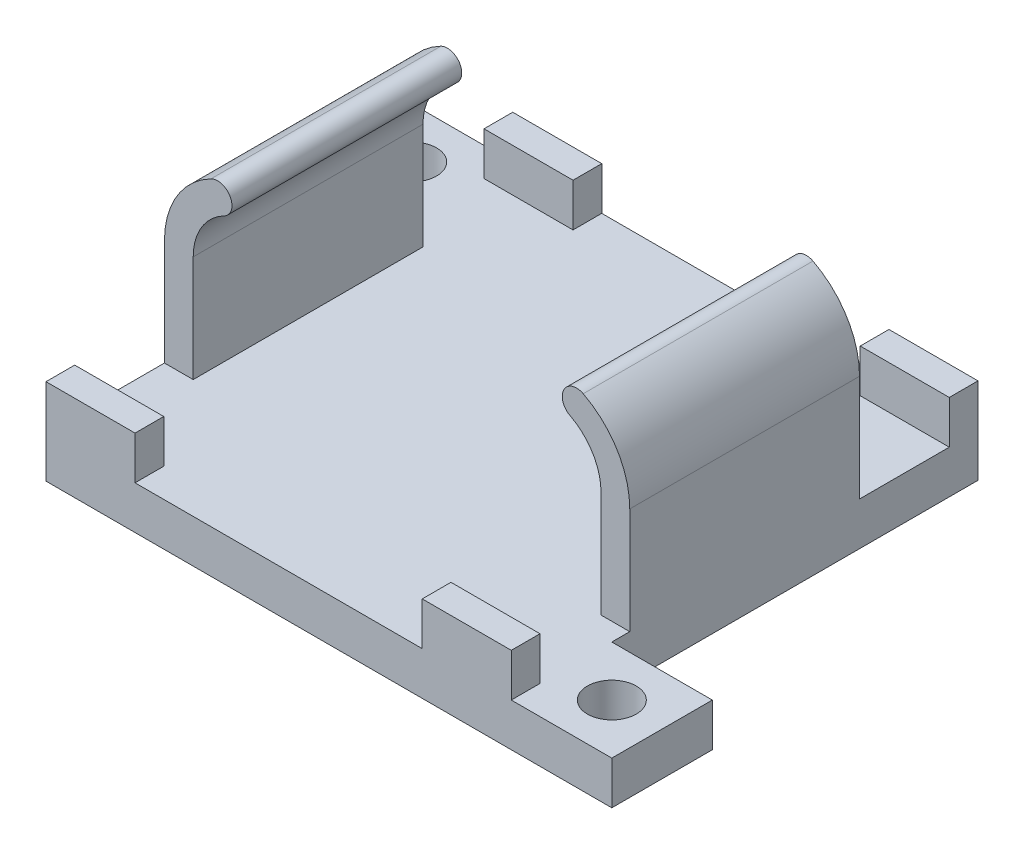
SolidWorks part; units mm, degrees
ref_plane "Front Plane" through (0, 0, 0) normal (0, 0, 1) x (1, 0, 0)
ref_plane "Top Plane" through (0, 0, 0) normal (0, 1, 0) x (1, 0, 0)
ref_plane "Right Plane" through (0, 0, 0) normal (1, 0, 0) x (0, 0, -1)
sketch "Sketch1" plane through (0, 0, 0) normal (0, 0, 1) x (1, 0, 0)
  line L0 (-16.2, -2.2) -> (16.2, -2.2)
  line L1 (-10.2, 8.2) -> (10.2, 8.2)
  line L2 (-16.2, 2.2) -> (-16.2, -8.2)
  line L3 (-16.2, -8.2) -> (16.2, -8.2)
  line L4 (16.2, 2.2) -> (16.2, -8.2)
  line L5 (-16.2, 8.2) -> (16.2, -8.2) construction
  line L6 (-16.2, -8.2) -> (16.2, 8.2) construction
  line L7 (-10.2, 6.2) -> (10.2, 6.2)
  line L8 (-14.2, 2.2) -> (-14.2, -5.2)
  line L9 (-14.2, -5.2) -> (14.2, -5.2)
  line L10 (14.2, 2.2) -> (14.2, -5.2)
  line L11 (-16.2, -5.2) -> (16.2, -5.2)
  line L17 (-10, 4) -> (10, 4)
  line L18 (-10, 4) -> (-10, -5.2)
  line L19 (-10, -5.2) -> (10, -5.2)
  line L20 (10, 4) -> (10, -5.2)
  arc A0 (14.2, 2.2) -> (10.2, 6.2) centre (10.2, 2.2) ccw
  arc A1 (-14.2, 2.2) -> (-10.2, 6.2) centre (-10.2, 2.2) cw
  arc A2 (16.2, 2.2) -> (10.2, 8.2) centre (10.2, 2.2) ccw
  arc A3 (-16.2, 2.2) -> (-10.2, 8.2) centre (-10.2, 2.2) cw
  circle A4 centre (-12.5, 6.6396) radius 1
  circle A5 centre (12.5, 6.6396) radius 1
  point P0 (0, 0)
  point P10 (0, -5.2)
  point P15 (-14.2, 6.2)
  point P30 (0, 0)
  point P35 (0, 4)
  dimension "D5" = 4
  dimension "D6" = 6
  dimension "D9" = 12.5
  dimension "D1" = 11.4
  dimension "D2" = 3
  dimension "D3" = 2
  dimension "D4" = 28.4
  dimension "D7" = 2
  dimension "D8" = 12.5
  dimension "D10" = 4
  dimension "D11" = 20
  dimension "D12" = 3
extrude "Boss-Extrude1" add sketch "Sketch1" along normal blind 14.25 and the other way blind 14.25 contours L11 L2 L3 L4 L9 region at (0, -6.7, 0)
extrude "Boss-Extrude2" add sketch "Sketch1<3>" along normal blind 2 from surface contours L11 L2 L3 L4 L9 | L2 L11 L8 L0 | L18 L0 L8 L9 | L0 L20 L9 L10 | L10 L11 L4 L0 region at (-15.2, -3.7, 0) region at (-12.1, -3.7, 0) region at (0, -6.7, 0) region at (12.1, -3.7, 0) region at (15.2, -3.7, 0) starting at face at (0, -6.7, 14.25)
sketch "Sketch1<3>" plane through (0, 0, 0) normal (0, 0, 1) x (1, 0, 0) same geometry as "Sketch1"
extrude "Boss-Extrude3" add sketch "Sketch1<6>" against normal blind 2 from surface contours L2 L11 L8 L0 | L18 L0 L8 L9 | L11 L2 L3 L4 L9 | L0 L20 L9 L10 | L10 L11 L4 L0 region at (-15.2, -3.7, 0) region at (-12.1, -3.7, 0) region at (0, -6.7, 0) region at (12.1, -3.7, 0) region at (15.2, -3.7, 0) starting at face at (0, -6.7, -14.25)
sketch "Sketch1<6>" plane through (0, 0, 0) normal (0, 0, 1) x (1, 0, 0) same geometry as "Sketch1"
extrude "Boss-Extrude4" add sketch "Sketch1<7>" along normal blind 8 and the other way blind 8 contours L2 L11 L8 L0 | A4 A3 L2 L0 L8 A1 | A4 | A5 | A5 A0 L10 L0 L4 A2 | L10 L11 L4 L0 region at (-14.8694, 2.2734, 0) region at (-15.2, -3.7, 0) region at (-12.5, 6.6396, 0) region at (14.8694, 2.2734, 0) region at (15.2, -3.7, 0) region at (12.5, 6.6396, 0)
sketch "Sketch1<7>" plane through (0, 0, 0) normal (0, 0, 1) x (1, 0, 0) same geometry as "Sketch1"
sketch "Sketch2" plane through (0, 0, 0) normal (0, 1, 0) x (1, 0, 0)
  line L0 (16.2, -8) -> (16.2, -14.25) construction
  line L1 (-23.2, 16.25) -> (-16.2, 16.25)
  line L2 (-23.2, 16.25) -> (-23.2, 9.25)
  line L3 (-23.2, 9.25) -> (-16.2, 9.25)
  line L4 (-16.2, 16.25) -> (-16.2, 9.25)
  line L5 (16.2, -9.25) -> (23.2, -9.25)
  line L6 (16.2, -9.25) -> (16.2, -16.25)
  line L7 (16.2, -16.25) -> (23.2, -16.25)
  line L8 (23.2, -9.25) -> (23.2, -16.25)
  line L9 (-16.2, 14.25) -> (-16.2, 8) construction
  line L10 (10, -16.25) -> (-10, -16.25) construction
  line L11 (-10, 16.25) -> (10, 16.25) construction
  circle A0 centre (-19.7, 12.75) radius 1.7
  circle A1 centre (19.7, -12.75) radius 1.7
  point P13 (23.2, -12.75)
  point P17 (-23.2, 12.75)
  dimension "D7" = 3.4
  dimension "D8" = 3.4
  dimension "D1" = 7
  dimension "D2" = 7
  dimension "D3" = 7
  dimension "D4" = 7
  dimension "D5" = 3.5
  dimension "D6" = 3.5
extrude "Boss-Extrude5" add sketch "Sketch2" along normal blind 3 from surface starting at face at (0, -8.2, 0)
sketch "Sketch3" plane through (0, 0, 0) normal (0, 1, 0) x (1, 0, 0)
  line L1 (-19.7, 12.75) -> (19.7, 12.75)
  line L2 (-19.7, 12.75) -> (-19.7, -12.75)
  line L3 (-19.7, -12.75) -> (19.7, -12.75)
  line L4 (19.7, 12.75) -> (19.7, -12.75)
  line L5 (-19.7, 12.75) -> (19.7, -12.75) construction
  line L6 (-19.7, -12.75) -> (19.7, 12.75) construction
  circle A0 centre (-19.7, 12.75) radius 1.7 construction
  circle A1 centre (19.7, -12.75) radius 1.7 construction
  point P0 (0, 0)
